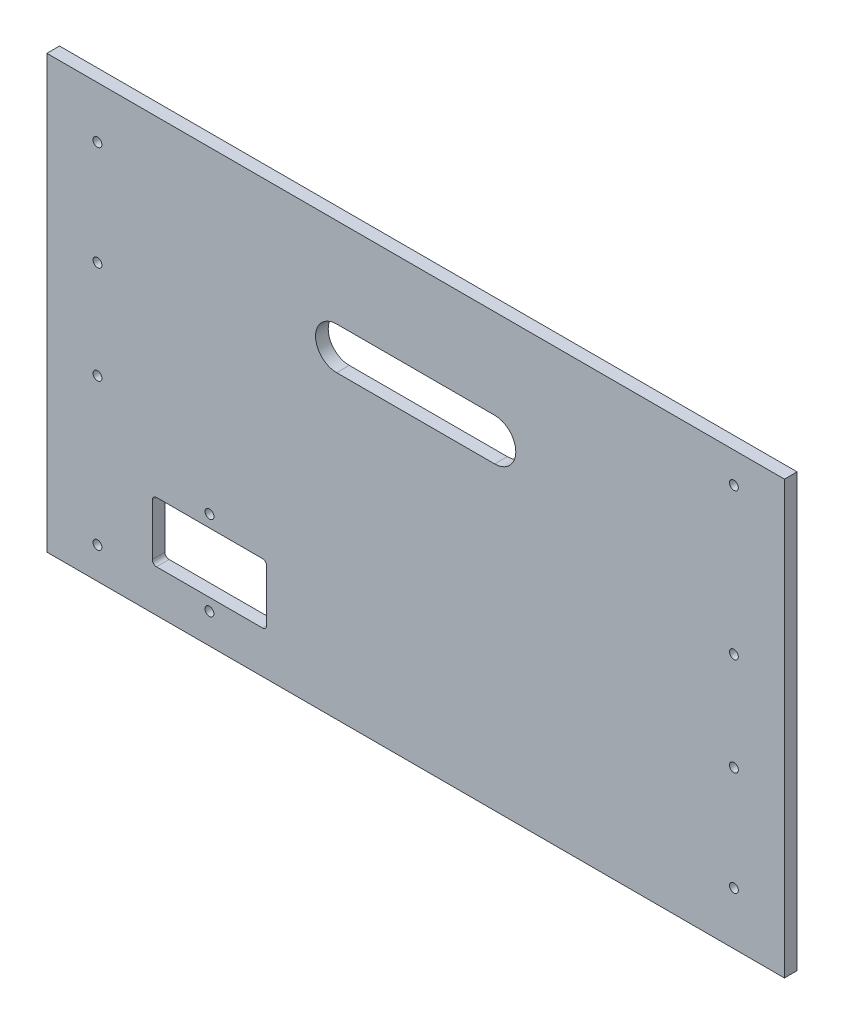
SolidWorks part; units mm, degrees
material "Acrílico (médio-alto impacto)"
ref_plane "Plano frontal" through (0, 0, 0) normal (0, 0, 1) x (1, 0, 0)
ref_plane "Plano superior" through (0, 0, 0) normal (0, 1, 0) x (1, 0, 0)
ref_plane "Plano direito" through (0, 0, 0) normal (1, 0, 0) x (0, 0, -1)
sketch "Esboço1" plane through (0, 0, 0) normal (0, 0, 1) x (1, 0, 0)
  line L5 (-175, -102.5) -> (175, -102.5)
  line L6 (-175, -102.5) -> (-175, 102.5)
  line L11 (-175, 102.5) -> (175, 102.5)
  line L25 (175, -102.5) -> (175, 102.5)
  line L26 (-175, -102.5) -> (175, 102.5) construction
  line L27 (-175, 102.5) -> (175, -102.5) construction
  point P0 (0, 0)
  dimension "D1" = 350
  dimension "D2" = 205
extrude "Ressalto-extrusão1" add sketch "Esboço1" along normal blind 6 contours L5 L25 L11 L6 region at (0, 0, 0)
sketch "Esboço2" plane through (0, 0, 6) normal (0, 0, 1) x (1, 0, 0)
  line L0 (-37.5, 50) -> (37.5, 50) construction
  line L1 (-37.5, 60) -> (37.5, 60)
  line L2 (-37.5, 40) -> (37.5, 40)
  line L3 (-175, 102.5) -> (175, 102.5) construction
  arc A0 (-37.5, 60) -> (-37.5, 40) centre (-37.5, 50) ccw
  arc A1 (37.5, 40) -> (37.5, 60) centre (37.5, 50) ccw
  point P2 (0, 50)
  dimension "D3" = 10
  dimension "D1" = 75
  dimension "D2" = 50
  dimension "D4" = 75
extrude "Corte-extrusão1" cut sketch "Esboço2" against normal through all
sketch "Esboço3" plane through (0, 0, 6) normal (0, 0, 1) x (1, 0, 0)
  line L0 (-175, -102.5) -> (-175, 102.5) construction
  line L1 (-123, -82.5) -> (-72.7, -82.5)
  line L2 (-125, -80.5) -> (-125, -56)
  line L3 (-123, -54) -> (-72.7, -54)
  line L4 (-70.7, -80.5) -> (-70.7, -56)
  line L5 (-125, -82.5) -> (-70.7, -54) construction
  line L6 (-125, -54) -> (-70.7, -82.5) construction
  line L7 (-175, -102.5) -> (175, -102.5) construction
  arc A0 (-123, -82.5) -> (-125, -80.5) centre (-123, -80.5) cw
  arc A1 (-72.7, -82.5) -> (-70.7, -80.5) centre (-72.7, -80.5) ccw
  arc A2 (-72.7, -54) -> (-70.7, -56) centre (-72.7, -56) cw
  arc A3 (-125, -56) -> (-123, -54) centre (-123, -56) cw
  circle A4 centre (-97.85, -48.25) radius 2.1
  circle A5 centre (-97.85, -88.25) radius 2.1
  point P0 (-97.85, -68.25)
  dimension "D3" = 2
  dimension "D4" = 4.2
  dimension "D5" = 4.2
  dimension "D6" = 40
  dimension "D1" = 54.3
  dimension "D2" = 28.5
  dimension "D7" = 20
  dimension "D8" = 50
  dimension "D9" = 20
extrude "Corte-extrusão2" cut sketch "Esboço3" against normal through all
hole_wizard "Furo de diâmetro Ø4.2 (4.2)1" positions "Esboço4" profile "Esboço5" hole size "Ø4.2" standard "ISO" end condition through all
sketch "Esboço4" plane through (0, 0, 6) normal (0, 0, 1) x (1, 0, 0)
  point P0 (-151, -87.5)
  point P3 (-151, -18)
  point P6 (151, -28)
  point P9 (151, -77.5)
  point P13 (151, 88)
  point P16 (151, 18.5)
  point P19 (-151, 78)
  point P22 (-151, 28.5)
sketch "Esboço5" plane through (-151, -87.5, 6) normal (1, 0, 0) x (0, -1, 0)
  line L0 (0, 0) -> (0, 6)
  line L1 (0, 6) -> (2.1, 6)
  line L2 (2.1, 6) -> (2.1, 0)
  line L5 (2.1, 0) -> (0, 0)
  line L11 (0, -6.35) -> (0, 107.95) construction
  dimension "Thru Hole Dia." = 4.2
  dimension "Thru Hole Depth" = 6
